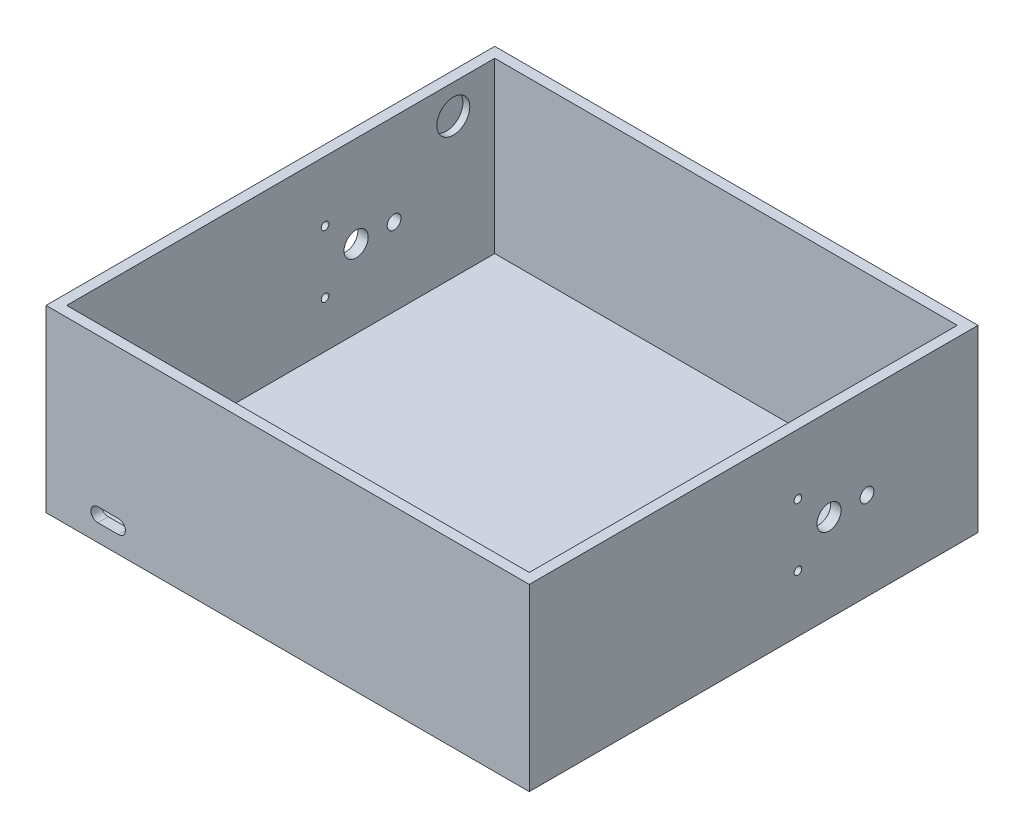
SolidWorks part; units mm, degrees
ref_plane "Front Plane" through (0, 0, 0) normal (0, 0, 1) x (1, 0, 0)
ref_plane "Top Plane" through (0, 0, 0) normal (0, 1, 0) x (1, 0, 0)
ref_plane "Right Plane" through (0, 0, 0) normal (1, 0, 0) x (0, 0, -1)
sketch "Sketch1" plane through (0, 0, 0) normal (0, 1, 0) x (1, 0, 0)
  line L1 (-70, 65) -> (70, 65)
  line L2 (-70, 65) -> (-70, -65)
  line L3 (-70, -65) -> (70, -65)
  line L4 (70, 65) -> (70, -65)
  line L5 (-70, 65) -> (70, -65) construction
  line L6 (-70, -65) -> (70, 65) construction
  point P0 (0, 0)
  dimension "D1" = 130
  dimension "D2" = 140
extrude "Boss-Extrude1" add sketch "Sketch1" along normal blind 52
shell "Shell1" thickness 3 removed face at (0, 52, 0)
sketch "Sketch2" plane through (70, 0, 0) normal (1, 0, 0) x (0, 0, -1)
  line L0 (-65, 0) -> (65, 0) construction
  line L1 (65, 52) -> (65, 0) construction
  circle A0 centre (21.8376, 25.5) radius 3.5
  circle A1 centre (32.8376, 25.5) radius 2
  circle A2 centre (12.8376, 34.5) radius 1.1
  circle A3 centre (12.8376, 16.5) radius 1.1
  dimension "D1" = 7
  dimension "D2" = 4
  dimension "D9" = 2.2
  dimension "D3" = 25.5
  dimension "D4" = 43.1624
  dimension "D5" = 11
  dimension "D6" = 18
  dimension "D7" = 9
  dimension "D8" = 52.1624
extrude "Cut-Extrude1" cut sketch "Sketch2" against normal up to surface (3 mm away) up to face at (67, 27.5, 0)
mirror "Mirror1" about plane through (0, 0, 0) normal (1, 0, 0) of "Cut-Extrude1"
sketch "Sketch3" plane through (0, 3, 0) normal (0, 1, 0) x (1, 0, 0)
  line L0 (-70, -65) -> (70, -65) construction
  line L1 (0, 0) -> (0, -122.9827) construction
  circle A0 centre (-7, -59) radius 1.1
  circle A1 centre (7, -59) radius 1.1
  dimension "D2" = 2.2
  dimension "D1" = 14
  dimension "D3" = 6
extrude "Cut-Extrude2" cut sketch "Sketch3" against normal up to surface (3 mm away) up to face at (0, 0, 0)
sketch "Sketch6" plane through (0, 0, 62) normal (0, 0, -1) x (-1, 0, 0)
  line L4 (55, 7) -> (49, 7) construction
  line L5 (55, 5) -> (49, 5)
  line L6 (55, 9) -> (49, 9)
  line L7 (70, 0) -> (-70, 0) construction
  line L8 (70, 52) -> (70, 0) construction
  arc A0 (55, 5) -> (55, 9) centre (55, 7) ccw
  arc A1 (49, 9) -> (49, 5) centre (49, 7) ccw
  point P2 (52, 7)
  dimension "D2" = 2
  dimension "D1" = 7
  dimension "D3" = 18
  dimension "D4" = 6
extrude "Cut-Extrude4" cut sketch "Sketch6" against normal up to surface (3 mm away) up to face at (0, 26, 65)
sketch "Sketch7" plane through (-67, 0, 0) normal (1, 0, 0) x (0, 0, -1)
  line L0 (62, 52) -> (62, 3) construction
  line L1 (62, 52) -> (-62, 52) construction
  circle A0 centre (50, 43.5) radius 4.775
  point P2 (49.9195, 43.4817)
  dimension "D1" = 9.55
  dimension "D2" = 12
  dimension "D3" = 8.5
extrude "Cut-Extrude5" cut sketch "Sketch7" against normal blind 2
ref_axis "Axis1" through (0, 54.6, 0) along (0, -1, 0)
pattern_circular "CirPattern5" count 2 every 180 about axis through (0, 54.6, 0) along (0, -1, 0) of "Cut-Extrude5"
